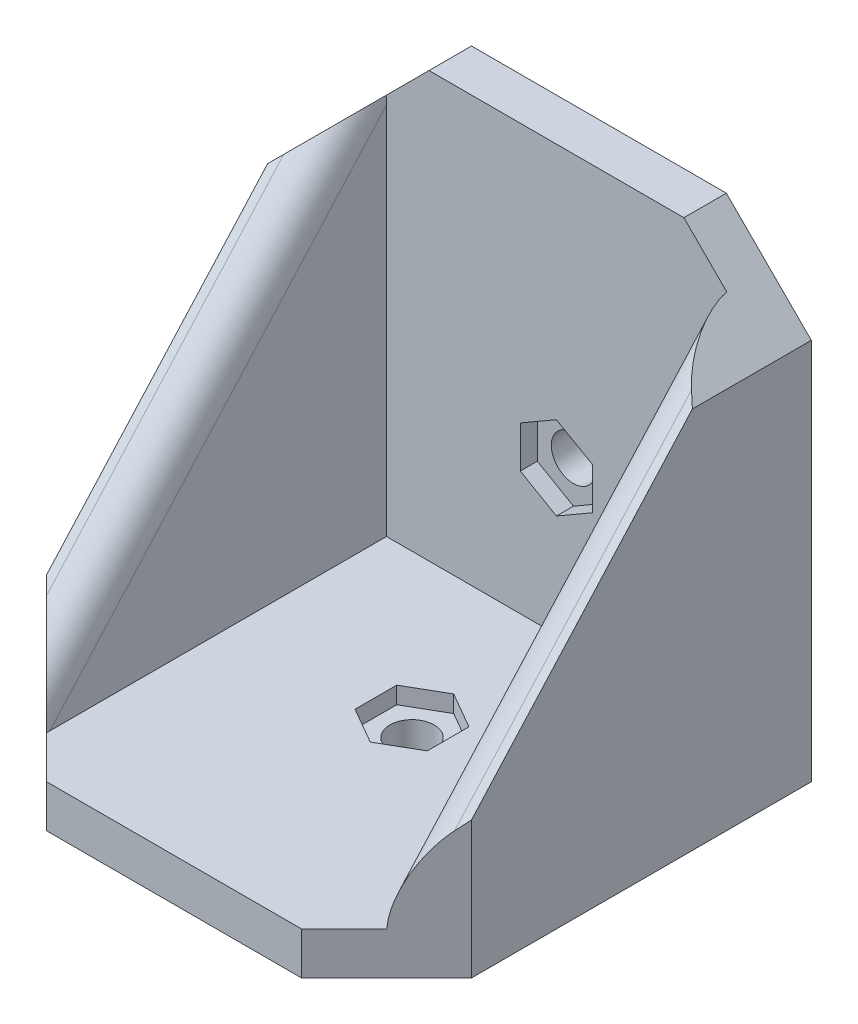
SolidWorks part; units mm, degrees
ref_plane "Front Plane" through (0, 0, 0) normal (0, 0, 1) x (1, 0, 0)
ref_plane "Top Plane" through (0, 0, 0) normal (0, 1, 0) x (1, 0, 0)
ref_plane "Right Plane" through (0, 0, 0) normal (1, 0, 0) x (0, 0, -1)
sketch "Sketch1" plane through (0, 0, 0) normal (0, 1, 0) x (1, 0, 0)
  line L1 (-25, 25) -> (25, 25)
  line L2 (-25, 25) -> (-25, -25)
  line L3 (-25, -25) -> (25, -25)
  line L4 (25, 25) -> (25, -25)
  line L5 (-25, 25) -> (25, -25) construction
  line L6 (-25, -25) -> (25, 25) construction
  point P0 (0, 0)
  dimension "D1" = 50
  dimension "D2" = 50
extrude "Boss-Extrude1" add sketch "Sketch1" along normal blind 5
sketch "Sketch2" plane through (0, 5, 0) normal (0, 1, 0) x (1, 0, 0)
  line L0 (-25, 25) -> (-25, -25) construction
  line L1 (-25, 20) -> (25, 20)
  line L2 (-25, 20) -> (-25, 25)
  line L3 (-25, 25) -> (25, 25)
  line L4 (25, 20) -> (25, 25)
  line L5 (-25, 20) -> (25, 25) construction
  line L6 (-25, 25) -> (25, 20) construction
  point P0 (0, 22.5)
  dimension "D1" = 5
extrude "Boss-Extrude2" add sketch "Sketch2" along normal blind 50
sketch "Sketch3" plane through (0, 0, -20) normal (0, 0, 1) x (1, 0, 0)
  line L0 (-25, 5) -> (25, 5) construction
  line L1 (0, 55) -> (0, 5) construction
  line L2 (-25, 55) -> (25, 55) construction
  line L3 (-25, 0) -> (25, 0) construction
  circle A0 centre (0, 22) radius 2.6
  point P8 (0, 0)
  dimension "D1" = 22
  dimension "D2" = 5.2
extrude "Cut-Extrude1" cut sketch "Sketch3" against normal blind 50
sketch "Sketch4" plane through (0, 5, 0) normal (0, 1, 0) x (1, 0, 0)
  line L0 (0, 20) -> (0, -25) construction
  line L1 (-25, 20) -> (25, 20) construction
  line L2 (-25, -25) -> (25, -25) construction
  line L3 (25, 25) -> (-25, 25) construction
  circle A0 centre (0, 3) radius 2.6
  point P8 (0, 0)
  dimension "D1" = 22
  dimension "D2" = 5.2
extrude "Cut-Extrude2" cut sketch "Sketch4" against normal blind 50
chamfer "Chamfer1" distance 10 angle 45 4 edges at (-25, 55, -22.5) (25, 55, -22.5) (25, 2.5, 25) (-25, 2.5, 25)
sketch "Sketch5" plane through (0, 0, -20) normal (0, 0, 1) x (1, 0, 0)
  line L1 (0, 26.9075) -> (-4.25, 24.4537)
  line L2 (-4.25, 24.4537) -> (-4.25, 19.5463)
  line L3 (-4.25, 19.5463) -> (0, 17.0925)
  line L4 (0, 17.0925) -> (4.25, 19.5463)
  line L5 (4.25, 19.5463) -> (4.25, 24.4537)
  line L6 (4.25, 24.4537) -> (0, 26.9075)
  circle A0 centre (0, 22) radius 4.25 construction
  dimension "D1" = 8.5
extrude "Cut-Extrude3" cut sketch "Sketch5" against normal offset from surface (2 mm away) 3 up to face at (2.6, 22, -25)
sketch "Sketch6" plane through (0, 5, 0) normal (0, 1, 0) x (1, 0, 0)
  line L1 (0, 7.9075) -> (-4.25, 5.4537)
  line L2 (-4.25, 5.4537) -> (-4.25, 0.5463)
  line L3 (-4.25, 0.5463) -> (0, -1.9075)
  line L4 (0, -1.9075) -> (4.25, 0.5463)
  line L5 (4.25, 0.5463) -> (4.25, 5.4537)
  line L6 (4.25, 5.4537) -> (0, 7.9075)
  circle A0 centre (0, 3) radius 4.25 construction
  dimension "D1" = 8.5
extrude "Cut-Extrude4" cut sketch "Sketch6" against normal offset from surface (2 mm away) 3 up to face at (0, 0, -0.4)
sketch "Sketch7" plane through (-25, 0, 0) normal (-1, 0, 0) x (0, 0, 1)
  line L0 (-20, 55) -> (25, 5)
  line L1 (25, 5) -> (-20, 5)
  line L2 (-20, 5) -> (-20, 55)
extrude "Boss-Extrude3" add sketch "Sketch7" against normal blind 5 from surface starting at face at (-25, 16.6667, -10)
extrude "Boss-Extrude4" add sketch "Sketch7<2>" along normal blind 5 from surface starting at face at (25, 16.6667, -10)
sketch "Sketch7<2>" plane through (-25, 0, 0) normal (-1, 0, 0) x (0, 0, 1) same geometry as "Sketch7"
sketch "Sketch8" plane through (0, 0, 0) normal (0, -1, 0) x (1, 0, 0)
  line L0 (-25, 15) -> (-15, 25)
  line L1 (-15, 25) -> (15, 25)
  line L2 (15, 25) -> (25, 15)
  line L3 (25, 15) -> (34.6886, 13.8685)
  line L4 (34.6886, 13.8685) -> (41.4807, 39.4385)
  line L5 (41.4807, 39.4385) -> (-8.1411, 43.6735)
  line L6 (-8.1411, 43.6735) -> (-46.8956, 41.556)
  line L7 (-46.8956, 41.556) -> (-45.5658, 17.2186)
  line L8 (-45.5658, 17.2186) -> (-29.3961, 9.154)
  line L9 (-29.3961, 9.154) -> (-25, 15)
extrude "Cut-Extrude5" cut sketch "Sketch8" against normal through all both and the other way through all
sketch "Sketch9" plane through (0, 0, -25) normal (0, 0, -1) x (-1, 0, 0)
  line L0 (-25, 45) -> (-15, 55)
  line L1 (-15, 55) -> (15, 55)
  line L2 (15, 55) -> (25, 45)
  line L3 (25, 45) -> (34.2159, 41.5737)
  line L4 (34.2159, 41.5737) -> (36.3327, 61.3745)
  line L5 (36.3327, 61.3745) -> (-31.0782, 63.764)
  line L6 (-31.0782, 63.764) -> (-33.6316, 52.6384)
  line L7 (-33.6316, 52.6384) -> (-28.0385, 40.0538)
  line L8 (-28.0385, 40.0538) -> (-25, 45)
extrude "Cut-Extrude6" cut sketch "Sketch9" against normal through all both
fillet "Fillet1" radius 4 2 edges at (20, 30.2778, 2.25) (-20, 30.2778, 2.25)
